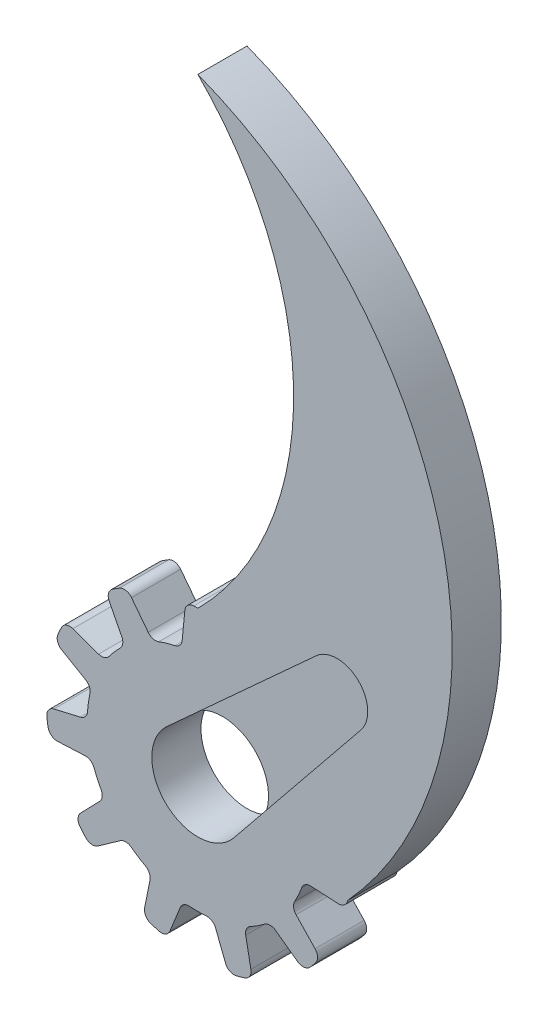
SolidWorks part; units mm, degrees
material "ABS"
ref_plane "Plano frontal" through (0, 0, 0) normal (0, 0, 1) x (1, 0, 0)
ref_plane "Plano superior" through (0, 0, 0) normal (0, 1, 0) x (1, 0, 0)
ref_plane "Plano direito" through (0, 0, 0) normal (1, 0, 0) x (0, 0, -1)
sketch "Esboço1" plane through (0, 0, 0) normal (0, 0, 1) x (1, 0, 0)
  line L0 (5.4289, 10.4113) -> (4.0402, 8.6536)
  line L1 (7.2321, 9.242) -> (6.1976, 7.2764)
  line L2 (10.1959, 5.8234) -> (8.0773, 5.0956)
  line L3 (11.0806, 3.8649) -> (9.1477, 2.7707)
  line L4 (11.7257, -0.6133) -> (9.5499, -0.0802)
  line L5 (11.4112, -2.7393) -> (9.1935, -2.6148)
  line L6 (9.5327, -6.8553) -> (7.9905, -5.2306)
  line L7 (8.1187, -8.4738) -> (6.3204, -7.1701)
  line L8 (4.3131, -10.9208) -> (3.8942, -8.7202)
  line L9 (2.2487, -11.5179) -> (1.4406, -9.4489)
  line L10 (-1.0616, 11.6936) -> (-1.2797, 9.4641)
  line L11 (1.0874, 11.6849) -> (1.2798, 9.472)
  line L12 (-2.2758, -11.519) -> (-1.4385, -9.4413)
  line L13 (-4.3354, -10.9052) -> (-3.8965, -8.7278)
  line L14 (-8.1422, -8.46) -> (-6.3145, -7.1648)
  line L15 (-9.5429, -6.8302) -> (-7.9966, -5.2356)
  line L16 (-11.4235, -2.715) -> (-9.1857, -2.6136)
  line L17 (-11.7207, -0.5866) -> (-9.5577, -0.0812)
  line L18 (-11.0779, 3.892) -> (-9.1405, 2.7675)
  line L19 (-10.1772, 5.8432) -> (-8.0844, 5.099)
  line L20 (-7.2152, 9.2633) -> (-6.1933, 7.2699)
  line L21 (-5.4025, 10.4178) -> (-4.0443, 8.6603)
  arc A0 (-1.8703, 8.8035) -> (-3.1854, 8.4174) centre (0, 0) ccw
  circle A1 centre (0, 0) radius 3.75
  arc A2 (0.3622, 12.3696) -> (-0.3355, 12.3703) centre (0, 0) ccw
  arc A3 (1.0874, 11.6849) -> (0.3622, 12.3696) centre (0.3402, 11.6199) ccw
  arc A4 (-1.0616, 11.6936) -> (-0.3355, 12.3703) centre (-0.3152, 11.6206) cw
  arc A5 (6.9922, 10.2102) -> (6.4056, 10.588) centre (0, 0) ccw
  arc A6 (7.2321, 9.242) -> (6.9922, 10.2102) centre (6.5684, 9.5913) ccw
  arc A7 (5.4289, 10.4113) -> (6.4056, 10.588) centre (6.0174, 9.9463) cw
  arc A8 (11.4022, 4.8091) -> (11.1131, 5.444) centre (0, 0) ccw
  arc A9 (11.0806, 3.8649) -> (11.4022, 4.8091) centre (10.7112, 4.5176) ccw
  arc A10 (10.1959, 5.8234) -> (11.1131, 5.444) centre (10.4395, 5.1141) cw
  arc A11 (12.1921, -2.1188) -> (12.2922, -1.4284) centre (0, 0) ccw
  arc A12 (11.4112, -2.7393) -> (12.1921, -2.1188) centre (11.4532, -1.9904) ccw
  arc A13 (11.7257, -0.6133) -> (12.2922, -1.4284) centre (11.5472, -1.3418) cw
  arc A14 (9.1111, -8.3741) -> (9.5686, -7.8473) centre (0, 0) ccw
  arc A15 (8.1187, -8.4738) -> (9.1111, -8.3741) centre (8.5589, -7.8665) ccw
  arc A16 (9.5327, -6.8553) -> (9.5686, -7.8473) centre (8.9887, -7.3717) cw
  arc A17 (3.1374, -11.9706) -> (3.8071, -11.7747) centre (0, 0) ccw
  arc A18 (2.2487, -11.5179) -> (3.1374, -11.9706) centre (2.9473, -11.2451) ccw
  arc A19 (4.3131, -10.9208) -> (3.8071, -11.7747) centre (3.5763, -11.0611) cw
  arc A20 (-3.8324, -11.7665) -> (-3.1632, -11.9638) centre (0, 0) ccw
  arc A21 (-4.3354, -10.9052) -> (-3.8324, -11.7665) centre (-3.6001, -11.0534) ccw
  arc A22 (-2.2758, -11.519) -> (-3.1632, -11.9638) centre (-2.9715, -11.2387) cw
  arc A23 (-9.5855, -7.8266) -> (-9.1291, -8.3544) centre (0, 0) ccw
  arc A24 (-9.5429, -6.8302) -> (-9.5855, -7.8266) centre (-9.0045, -7.3523) ccw
  arc A25 (-8.1422, -8.46) -> (-9.1291, -8.3544) centre (-8.5759, -7.8481) cw
  arc A26 (-12.2952, -1.4019) -> (-12.1967, -2.0926) centre (0, 0) ccw
  arc A27 (-11.7207, -0.5866) -> (-12.2952, -1.4019) centre (-11.55, -1.3169) ccw
  arc A28 (-11.4235, -2.715) -> (-12.1967, -2.0926) centre (-11.4575, -1.9658) cw
  arc A29 (-11.1013, 5.4679) -> (-11.3918, 4.8336) centre (0, 0) ccw
  arc A30 (-10.1772, 5.8432) -> (-11.1013, 5.4679) centre (-10.4285, 5.1365) ccw
  arc A31 (-11.0779, 3.892) -> (-11.3918, 4.8336) centre (-10.7014, 4.5407) cw
  arc A32 (-6.3828, 10.6017) -> (-6.9702, 10.2252) centre (0, 0) ccw
  arc A33 (-5.4025, 10.4178) -> (-6.3828, 10.6017) centre (-5.996, 9.9592) ccw
  arc A34 (-7.2152, 9.2633) -> (-6.9702, 10.2252) centre (-6.5477, 9.6055) cw
  arc A35 (-6.3329, 6.3948) -> (-7.2305, 5.359) centre (0, 0) ccw
  arc A36 (-8.7849, 1.9559) -> (-8.98, 0.5992) centre (0, 0) ccw
  arc A37 (-8.4477, -3.1041) -> (-7.8784, -4.3509) centre (0, 0) ccw
  arc A38 (-5.4285, -7.1785) -> (-4.2755, -7.9196) centre (0, 0) ccw
  arc A39 (-0.6857, -8.9738) -> (0.6849, -8.9739) centre (0, 0) ccw
  arc A40 (4.2748, -7.92) -> (5.4278, -7.179) centre (0, 0) ccw
  arc A41 (7.878, -4.3516) -> (8.4475, -3.1049) centre (0, 0) ccw
  arc A42 (8.9801, 0.5984) -> (8.7851, 1.9551) centre (0, 0) ccw
  arc A43 (7.231, 5.3584) -> (6.3335, 6.3943) centre (0, 0) ccw
  arc A44 (3.1862, 8.4171) -> (1.8711, 8.8034) centre (0, 0) ccw
  arc A45 (6.3204, -7.1701) -> (5.4278, -7.179) centre (5.8802, -7.7773) ccw
  arc A46 (3.8942, -8.7202) -> (4.2748, -7.92) centre (4.631, -8.58) cw
  arc A47 (1.4406, -9.4489) -> (0.6849, -8.9739) centre (0.742, -9.7217) ccw
  arc A48 (-1.4385, -9.4413) -> (-0.6857, -8.9738) centre (-0.7429, -9.7217) cw
  arc A49 (-3.8965, -8.7278) -> (-4.2755, -7.9196) centre (-4.6318, -8.5796) ccw
  arc A50 (-6.3145, -7.1648) -> (-5.4285, -7.1785) centre (-5.8809, -7.7768) cw
  arc A51 (-7.9966, -5.2356) -> (-7.8784, -4.3509) centre (-8.535, -4.7135) ccw
  arc A52 (-9.1857, -2.6136) -> (-8.4477, -3.1041) centre (-9.1517, -3.3628) cw
  arc A53 (-9.5577, -0.0812) -> (-8.98, 0.5992) centre (-9.7284, 0.6491) ccw
  arc A54 (-9.1405, 2.7675) -> (-8.7849, 1.9559) centre (-9.517, 2.1188) cw
  arc A55 (-8.0844, 5.099) -> (-7.2305, 5.359) centre (-7.8331, 5.8056) ccw
  arc A56 (7.9905, -5.2306) -> (7.878, -4.3516) centre (8.5345, -4.7143) cw
  arc A57 (9.1935, -2.6148) -> (8.4475, -3.1049) centre (9.1514, -3.3636) ccw
  arc A58 (9.5499, -0.0802) -> (8.9801, 0.5984) centre (9.7284, 0.6482) cw
  arc A59 (9.1477, 2.7707) -> (8.7851, 1.9551) centre (9.5172, 2.118) ccw
  arc A60 (8.0773, 5.0956) -> (7.231, 5.3584) centre (7.8336, 5.8049) cw
  arc A61 (6.1976, 7.2764) -> (6.3335, 6.3943) centre (6.8613, 6.9271) ccw
  arc A62 (4.0402, 8.6536) -> (3.1862, 8.4171) centre (3.4517, 9.1186) cw
  arc A63 (1.8711, 8.8034) -> (1.2798, 9.472) centre (2.027, 9.537) cw
  arc A64 (-1.8703, 8.8035) -> (-1.2797, 9.4641) centre (-2.0261, 9.5372) ccw
  arc A65 (-4.0443, 8.6603) -> (-3.1854, 8.4174) centre (-3.4509, 9.1189) ccw
  arc A66 (-6.1933, 7.2699) -> (-6.3329, 6.3948) centre (-6.8607, 6.9278) cw
  point P94 (0, 0)
  dimension "D1" = 7.5
  dimension "D2" = 11
extrude "Ressalto-extrusão1" add sketch "Esboço1" along normal blind 4
sketch "Esboço6" plane through (0, 0, 4) normal (0, 0, 1) x (1, 0, 0)
  line L0 (0, 50) -> (0, 0) construction
  line L1 (-18.815, 31.185) -> (0, 50) construction
  line L2 (-18.815, 31.185) -> (0, 12.37) construction
  line L3 (0, 9) -> (0, 12.37)
  line L4 (12.1921, -2.1188) -> (8.8671, -1.541)
  arc A1 (0, 12.37) -> (0, 50) centre (-18.815, 31.185) ccw
  arc A2 (12.1921, -2.1188) -> (0, 50) centre (-11.7234, 19.7721) ccw
  arc A4 (8.8671, -1.541) -> (0, 9) centre (0, 0) ccw
  dimension "D2" = 90
  dimension "D1" = 50
extrude "Ressalto-extrusão2" add sketch "Esboço6" against normal blind 4 contours A4 L4 A2 A1 L3 region at (11.6052, 20.8361, 4)
sketch "Esboço7" plane through (0, 0, 4) normal (0, 0, 1) x (1, 0, 0)
  line L0 (0, 0) -> (11.3245, 12.0002) construction
  line L1 (-2.5245, 2.773) -> (9.6415, 13.8489)
  line L2 (2.9145, -2.3597) -> (13.2675, 10.4271)
  arc A0 (13.2675, 10.4271) -> (9.6415, 13.8489) centre (11.3245, 12.0002) ccw
  arc A1 (-2.5245, 2.773) -> (2.9145, -2.3597) centre (0, 0) ccw
  circle A2 centre (0, 0) radius 3.75 construction
  dimension "D1" = 2.5
  dimension "D2" = 16.5
extrude "Corte-extrusão1" cut sketch "Esboço7" against normal blind 2
